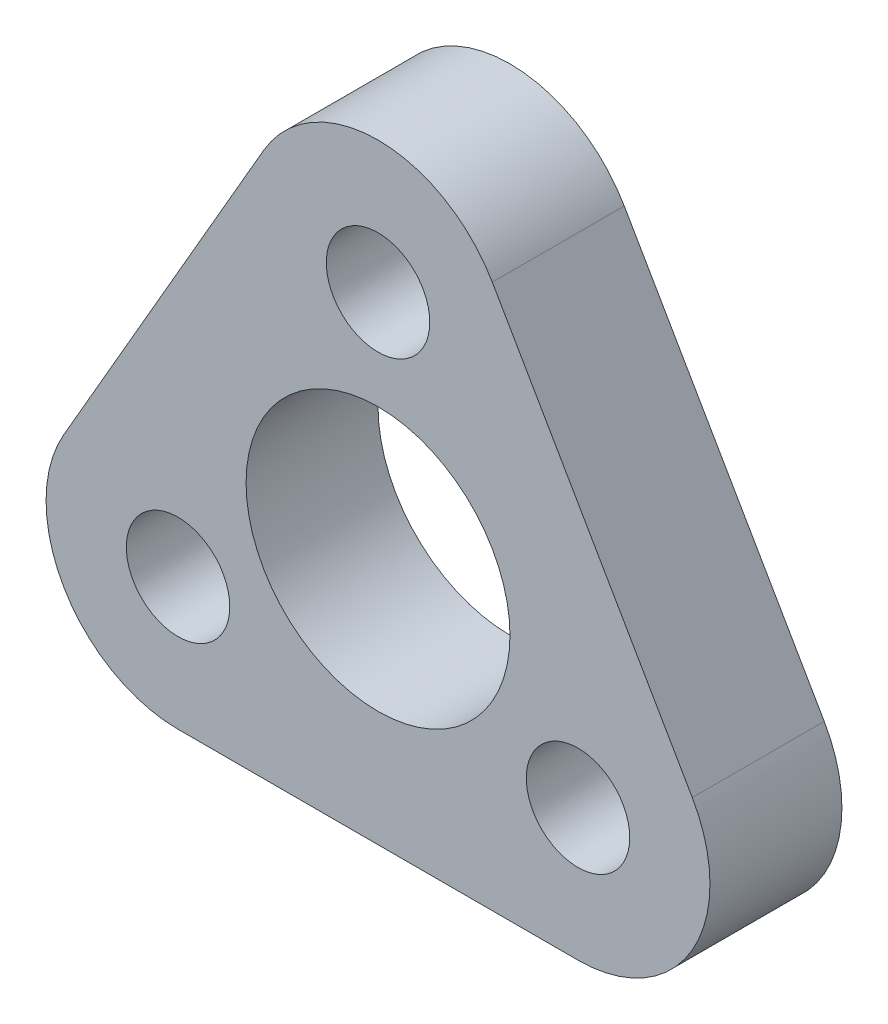
SolidWorks part; units mm, degrees
material "6061-T6 (SS)"
ref_plane "Front Plane" through (0, 0, 0) normal (0, 0, 1) x (1, 0, 0)
ref_plane "Top Plane" through (0, 0, 0) normal (0, 1, 0) x (1, 0, 0)
ref_plane "Right Plane" through (0, 0, 0) normal (1, 0, 0) x (0, 0, -1)
sketch "Sketch1" plane through (0, 0, 0) normal (0, 0, 1) x (1, 0, 0)
  line L3 (0, 11.1125) -> (9.6237, -5.5562) construction
  line L4 (9.6237, -5.5562) -> (-9.6237, -5.5563) construction
  line L5 (-9.6237, -5.5563) -> (0, 11.1125) construction
  line L6 (0, 23.8125) -> (20.6222, -11.9062)
  line L7 (20.6222, -11.9062) -> (-20.6222, -11.9062)
  line L8 (-20.6222, -11.9062) -> (0, 23.8125)
  circle A0 centre (0, 0) radius 6.35
  circle A1 centre (0, 11.1125) radius 2.4892
  circle A2 centre (9.6237, -5.5562) radius 2.4892
  circle A3 centre (-9.6237, -5.5563) radius 2.4892
  point P11 (0, 0)
  dimension "D1" = 12.7
  dimension "D2" = 4.9784
  dimension "D3" = 11.1125
  dimension "D5" = 6.35
  dimension "D4" = 3
extrude "Boss-Extrude1" add sketch "Sketch1" along normal blind 6.35
fillet "Fillet1" radius 6.35 3 edges at (20.6222, -11.9062, 3.175) (-20.6222, -11.9062, 3.175) (0, 23.8125, 3.175)
